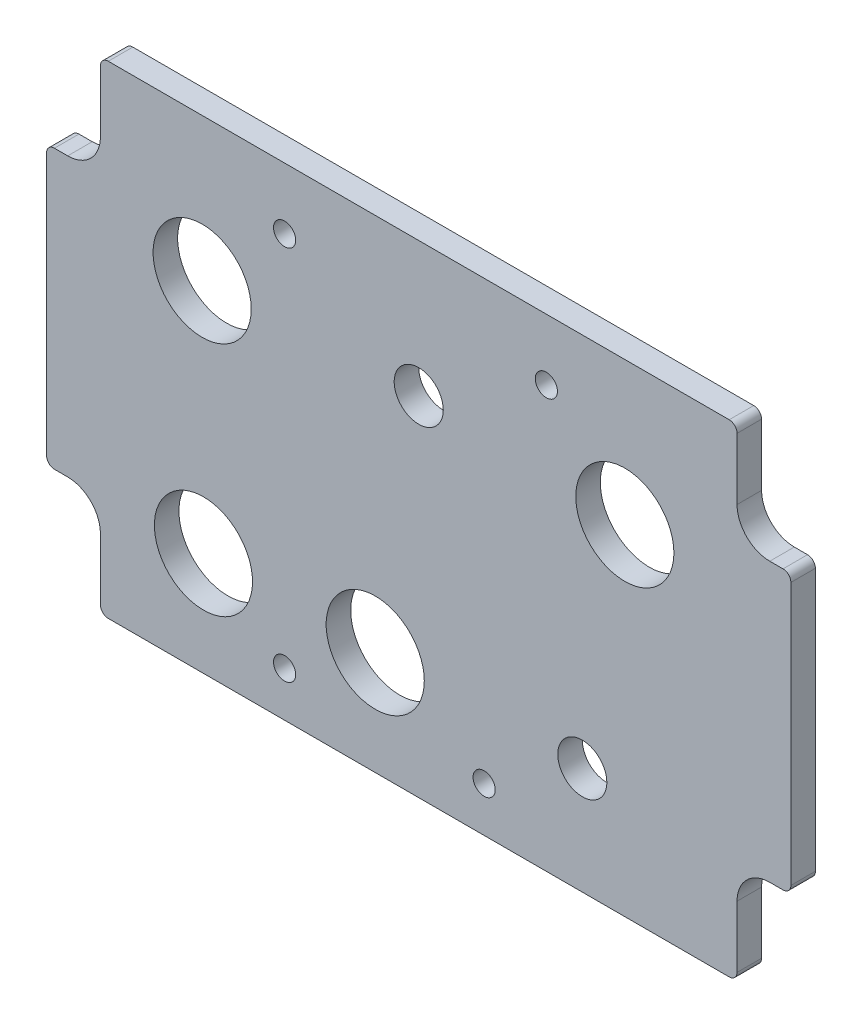
SolidWorks part; units mm, degrees
material "Acrylic (Medium-high impact)"
ref_plane "Front Plane" through (0, 0, 0) normal (0, 0, 1) x (1, 0, 0)
ref_plane "Top Plane" through (0, 0, 0) normal (0, 1, 0) x (1, 0, 0)
ref_plane "Right Plane" through (0, 0, 0) normal (1, 0, 0) x (0, 0, -1)
sketch "Sketch1" plane through (0, 0, 0) normal (0, 0, 1) x (1, 0, 0)
  line L24 (133.2865, 94.4562) -> (12.7635, 94.4562)
  line L25 (11.2395, 92.9322) -> (11.2395, 80.9625)
  line L26 (4.8895, 74.6125) -> (2.3177, 74.6125)
  line L27 (0.7937, 73.0885) -> (0.7937, 22.1615)
  line L28 (2.3177, 20.6375) -> (4.8895, 20.6375)
  line L29 (11.2395, 14.2875) -> (11.2395, 2.3178)
  line L30 (12.7635, 0.7938) -> (133.2865, 0.7938)
  line L31 (134.8105, 2.3178) -> (134.8105, 14.2875)
  line L32 (141.1605, 20.6375) -> (143.7322, 20.6375)
  line L33 (145.2562, 22.1615) -> (145.2562, 73.0885)
  line L34 (143.7322, 74.6125) -> (141.1605, 74.6125)
  line L35 (134.8105, 80.9625) -> (134.8105, 92.9322)
  arc A24 (134.8105, 92.9322) -> (133.2865, 94.4562) centre (133.2865, 92.9322) ccw
  arc A25 (12.7635, 94.4562) -> (11.2395, 92.9322) centre (12.7635, 92.9322) ccw
  arc A26 (4.8895, 74.6125) -> (11.2395, 80.9625) centre (4.8895, 80.9625) ccw
  arc A27 (2.3177, 74.6125) -> (0.7937, 73.0885) centre (2.3177, 73.0885) ccw
  arc A28 (0.7937, 22.1615) -> (2.3177, 20.6375) centre (2.3177, 22.1615) ccw
  arc A29 (11.2395, 14.2875) -> (4.8895, 20.6375) centre (4.8895, 14.2875) ccw
  arc A30 (11.2395, 2.3178) -> (12.7635, 0.7938) centre (12.7635, 2.3178) ccw
  arc A31 (133.2865, 0.7938) -> (134.8105, 2.3178) centre (133.2865, 2.3178) ccw
  arc A32 (141.1605, 20.6375) -> (134.8105, 14.2875) centre (141.1605, 14.2875) ccw
  arc A33 (143.7322, 20.6375) -> (145.2562, 22.1615) centre (143.7322, 22.1615) ccw
  arc A34 (145.2562, 73.0885) -> (143.7322, 74.6125) centre (143.7322, 73.0885) ccw
  arc A35 (134.8105, 80.9625) -> (141.1605, 74.6125) centre (141.1605, 80.9625) ccw
extrude "Boss-Extrude1" add sketch "Sketch1" along normal blind 4.7625
hole_wizard "#6 Clearance Hole1" positions "Sketch3" profile "Sketch2" hole size "#6" standard "ANSI Inch" end condition through all
sketch "Sketch3" plane through (0, 0, 4.7625) normal (0, 0, 1) x (1, 0, 0)
  point P0 (46.99, 82.55)
  point P3 (97.79, 82.55)
  point P6 (85.725, 9.525)
  point P9 (46.99, 9.525)
sketch "Sketch2" plane through (46.99, 82.55, 4.7625) normal (1, 0, 0) x (0, -1, 0)
  line L0 (0, 0) -> (0, 4.7625)
  line L1 (0, 4.7625) -> (2.1526, 4.7625)
  line L2 (2.1526, 4.7625) -> (2.1526, 0)
  line L5 (2.1526, 0) -> (0, 0)
  line L11 (0, -6.35) -> (0, 107.95) construction
  dimension "Thru Hole Dia." = 4.3053
  dimension "Thru Hole Depth" = 4.7625
sketch "Sketch4" plane through (0, 0, 4.7625) normal (0, 0, 1) x (1, 0, 0)
  circle A0 centre (73.025, 68.326) radius 4.7625 construction
  circle A1 centre (104.775, 21.59) radius 4.7625 construction
  circle A2 centre (73.025, 68.326) radius 4.7625
  circle A3 centre (104.775, 21.59) radius 4.7625
  circle A4 centre (30.988, 66.675) radius 9.525
  circle A5 centre (113.03, 66.675) radius 9.525
  circle A6 centre (31.242, 20.955) radius 9.525
  circle A7 centre (64.5795, 20.955) radius 9.525
  dimension "D1" = 19.05
extrude "Cut-Extrude1" cut sketch "Sketch4" against normal through all
